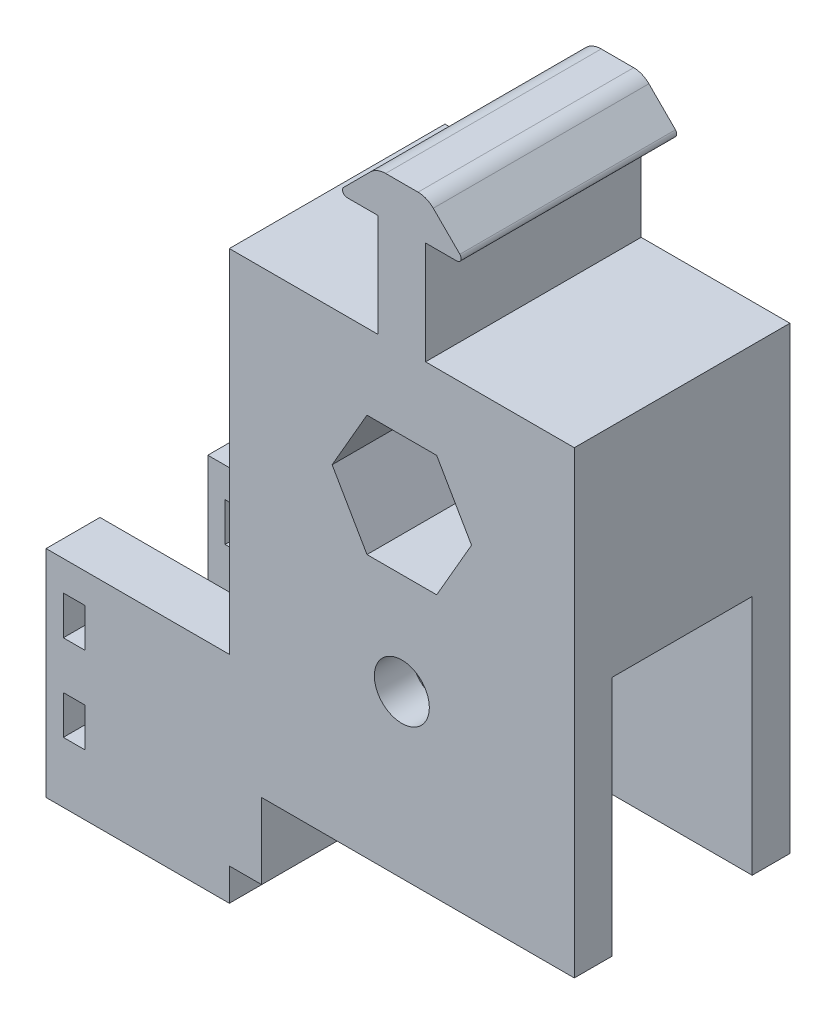
SolidWorks part; units mm, degrees
ref_plane "Front Plane" through (0, 0, 0) normal (0, 0, 1) x (1, 0, 0)
ref_plane "Top Plane" through (0, 0, 0) normal (0, 1, 0) x (1, 0, 0)
ref_plane "Right Plane" through (0, 0, 0) normal (1, 0, 0) x (0, 0, -1)
sketch "Sketch1" plane through (0, 0, 0) normal (0, 0, 1) x (1, 0, 0)
  line L0 (-20.32, 16.002) -> (-20.32, -38.1)
  line L1 (-4.1061, 7.112) -> (-8.2122, 0)
  line L2 (-8.2122, 0) -> (-4.1061, -7.112)
  line L3 (-4.1061, -7.112) -> (4.1061, -7.112)
  line L4 (4.1061, -7.112) -> (8.2122, 0)
  line L5 (8.2122, 0) -> (4.1061, 7.112)
  line L6 (4.1061, 7.112) -> (-4.1061, 7.112)
  line L7 (-20.32, -38.1) -> (20.32, -38.1)
  line L8 (20.32, -38.1) -> (20.32, 16.002)
  line L9 (-20.32, 16.002) -> (-2.794, 16.002)
  line L10 (-2.794, 16.002) -> (-2.794, 28.1305)
  line L11 (-2.794, 28.1305) -> (-6.477, 28.1305)
  line L12 (-6.8362, 28.9977) -> (-3.7065, 32.1275)
  line L13 (-1.9104, 32.8714) -> (1.9104, 32.8714)
  line L14 (0, 41.8096) -> (0, -25.778) construction
  line L15 (20.32, 16.002) -> (2.794, 16.002)
  line L16 (2.794, 16.002) -> (2.794, 28.1305)
  line L17 (6.8362, 28.9977) -> (3.7065, 32.1275)
  line L18 (2.794, 28.1305) -> (6.477, 28.1305)
  line L19 (-6.985, 28.6385) -> (6.985, 28.6385) construction
  circle A0 centre (0, 0) radius 7.112 construction
  arc A1 (-6.477, 28.1305) -> (-6.8362, 28.9977) centre (-6.477, 28.6385) cw
  arc A2 (-3.7065, 32.1275) -> (-1.9104, 32.8714) centre (-1.9104, 30.3314) cw
  arc A3 (3.7065, 32.1275) -> (1.9104, 32.8714) centre (1.9104, 30.3314) ccw
  arc A4 (6.477, 28.1305) -> (6.8362, 28.9977) centre (6.477, 28.6385) ccw
  point P18 (7.7034, 28.1305)
  point P21 (-4.6355, 28.1305)
  point P25 (-7.7034, 28.1305)
  point P29 (0, -38.1)
  point P35 (0, 32.8714)
  dimension "D7" = 0.508
  dimension "D8" = 2.54
  dimension "D1" = 14.224
  dimension "D2" = 21.0185
  dimension "D3" = 5.588
  dimension "D4" = 4.7409
  dimension "D5" = 135
  dimension "D6" = 13.97
  dimension "D9" = 38.1
  dimension "D10" = 8.89
  dimension "D11" = 20.32
extrude "Boss-Extrude1" add sketch "Sketch1" along normal mid plane 25.4
sketch "Sketch10" plane through (0, 0, 0) normal (0, 0, 1) x (1, 0, 0)
  line L0 (-20.32, -38.1) -> (-20.32, -46.99)
  line L1 (-20.32, -46.99) -> (-41.91, -46.99)
  line L2 (-41.91, -46.99) -> (-41.91, -50.8)
  line L3 (-41.91, -50.8) -> (-16.51, -50.8)
  line L4 (-16.51, -50.8) -> (-16.51, -38.1)
  line L5 (-20.32, -38.1) -> (20.32, -38.1) construction
  line L6 (-20.32, -38.1) -> (-16.51, -38.1)
  dimension "D2" = 8.89
  dimension "D3" = 3.81
  dimension "D4" = 21.59
extrude "Boss-Extrude4" add sketch "Sketch10" along normal up to surface and the other way up to surface up to face at (0, 18.0275, 12.7) other way up to face at (0, 18.0275, -12.7)
sketch "Sketch6" plane through (20.32, 0, 0) normal (1, 0, 0) x (0, 0, -1)
  line L0 (-12.7, -7.112) -> (12.7, -7.112) construction
  line L1 (-12.7, -7.112) -> (12.7, -7.112) construction
  line L2 (-8.255, -25.4) -> (-8.255, -9.652)
  line L3 (-8.255, -9.652) -> (8.255, -9.652)
  line L11 (-8.255, -25.4) -> (8.255, -25.4)
  line L12 (8.255, -9.652) -> (8.255, -25.4)
  point P10 (0, -9.652)
  dimension "D2" = 16.51
  dimension "D3" = 2.54
  dimension "D1" = 15.748
extrude "Cut-Extrude2" cut sketch "Sketch6" against normal through all
sketch "Sketch11" plane through (0, -46.99, 0) normal (0, 1, 0) x (1, 0, 0)
  line L0 (-41.91, -12.7) -> (-41.91, 12.7) construction
  line L1 (-20.32, -12.7) -> (-20.32, 12.7) construction
  line L2 (-41.91, -3.81) -> (-41.91, 3.81)
  line L3 (-20.32, -3.81) -> (-20.32, 3.81)
  line L4 (-41.91, 3.81) -> (-20.32, 3.81)
  line L5 (-41.91, -3.81) -> (-20.32, -3.81)
  point P8 (-20.32, 0)
  point P9 (-41.91, 0)
  dimension "D1" = 7.62
extrude "Cut-Extrude3" cut sketch "Sketch11" against normal up to surface (3.81 mm away) up to face at (-29.21, -50.8, 0)
sketch "Sketch15" plane through (0, 0, 12.7) normal (0, 0, 1) x (1, 0, 0)
  line L1 (-4.1061, -7.112) -> (4.1061, -7.112) construction
  circle A0 centre (0, -19.05) radius 3.2385
  point P7 (0, -7.112)
  dimension "D1" = 6.477
  dimension "D2" = 11.938
extrude "Cut-Extrude4" cut sketch "Sketch15" against normal up to surface (25.4 mm away) up to face at (-5.842, 4.643, -12.7)
sketch "Sketch16" plane through (20.32, 0, 0) normal (1, 0, 0) x (0, 0, -1)
  line L0 (-8.255, -25.4) -> (8.255, -25.4) construction
  line L1 (-8.255, -25.4) -> (8.255, -25.4)
  line L2 (-8.255, -25.4) -> (-8.255, -38.1)
  line L3 (-12.7, -38.1) -> (12.7, -38.1) construction
  line L4 (-8.255, -38.1) -> (8.255, -38.1)
  line L5 (8.255, -38.1) -> (8.255, -25.4)
extrude "Cut-Extrude5" cut sketch "Sketch16" against normal up to surface (36.83 mm away) up to face at (-16.51, -44.45, 0)
sketch "Sketch17" plane through (-20.32, 0, 0) normal (-1, 0, 0) x (0, 0, 1)
  line L0 (12.7, 16.002) -> (12.7, -46.99) construction
  line L1 (-3.81, -50.8) -> (-3.81, -46.99) construction
  line L2 (-3.81, -46.99) -> (-12.7, -46.99) construction
  line L3 (3.81, -50.8) -> (3.81, -46.99) construction
  line L4 (12.7, -46.99) -> (3.81, -46.99) construction
  line L5 (-3.81, -50.8) -> (3.81, -50.8) construction
  line L6 (-12.7, 16.002) -> (-12.7, -46.99) construction
  line L7 (12.7, -25.4) -> (12.7, -46.99)
  line L8 (-3.81, -50.8) -> (-3.81, -46.99)
  line L9 (-3.81, -46.99) -> (-12.7, -46.99)
  line L10 (3.81, -50.8) -> (3.81, -46.99)
  line L11 (12.7, -46.99) -> (3.81, -46.99)
  line L12 (-3.81, -50.8) -> (3.81, -50.8)
  line L13 (-12.7, -25.4) -> (-12.7, -46.99)
  line L14 (-12.7, -25.4) -> (12.7, -25.4)
  dimension "D1" = 21.59
extrude "Boss-Extrude5" add sketch "Sketch17" along normal blind 5.08
sketch "Sketch18" plane through (-25.4, 0, 0) normal (-1, 0, 0) x (0, 0, 1)
  line L0 (0, 0) -> (0, -56.8096) construction
  line L1 (-3.81, -46.99) -> (-12.7, -46.99) construction
  line L2 (-12.7, -25.4) -> (-12.7, -46.99) construction
  line L4 (-6.35, -46.99) -> (-12.7, -46.99)
  line L5 (-12.7, -25.4) -> (-12.7, -46.99)
  line L6 (12.7, -25.4) -> (-12.7, -25.4) construction
  line L7 (-6.35, -25.4) -> (-6.35, -46.99)
  line L8 (-6.35, -25.4) -> (-12.7, -25.4)
  line L9 (6.35, -25.4) -> (12.7, -25.4)
  line L10 (6.35, -25.4) -> (6.35, -46.99)
  line L11 (12.7, -25.4) -> (12.7, -46.99)
  line L12 (6.35, -46.99) -> (12.7, -46.99)
  dimension "D1" = 6.35
extrude "Boss-Extrude6" add sketch "Sketch18" along normal up to surface (16.51 mm away) up to face at (-41.91, -48.895, 8.255)
sketch "Sketch22" plane through (0, 0, 12.7) normal (0, 0, 1) x (1, 0, 0)
  line L0 (-20.32, -50.8) -> (-20.32, -46.99)
  line L1 (-16.51, -50.8) -> (-41.91, -50.8) construction
  line L2 (-20.32, -46.99) -> (-16.51, -46.99)
  line L4 (-16.51, -50.8) -> (-20.32, -50.8)
  line L5 (-16.51, -38.1) -> (-16.51, -50.8) construction
  line L6 (-16.51, -46.99) -> (-16.51, -50.8)
  dimension "D1" = 3.81
  dimension "D2" = 3.81
extrude "Cut-Extrude6" cut sketch "Sketch22" against normal up to surface (25.4 mm away) up to face at (-5.842, 6.802, -12.7)
sketch "Sketch23" plane through (0, 0, 12.7) normal (0, 0, 1) x (1, 0, 0)
  line L1 (-41.91, -25.4) -> (-20.32, -25.4) construction
  line L2 (-37.338, -25.4) -> (-37.338, -46.99) construction
  line L4 (-42.5372, -36.195) -> (-32.1388, -36.195) construction
  line L5 (-37.338, -28.9175) -> (-39.878, -28.9175)
  line L6 (-37.338, -28.9175) -> (-37.338, -33.4895)
  line L7 (-37.338, -33.4895) -> (-39.878, -33.4895)
  line L8 (-39.878, -28.9175) -> (-39.878, -33.4895)
  line L9 (-37.338, -39.0775) -> (-39.878, -39.0775)
  line L10 (-37.338, -39.0775) -> (-37.338, -43.6495)
  line L11 (-37.338, -43.6495) -> (-39.878, -43.6495)
  line L12 (-39.878, -39.0775) -> (-39.878, -43.6495)
  point P0 (-25.4, -25.4)
  point P20 (-37.338, -36.195)
  point P22 (-37.338, -36.195)
  point P23 (-39.878, -31.2035)
  point P24 (-39.878, -41.3635)
  dimension "D1" = 11.938
  dimension "D2" = 4.572
  dimension "D3" = 2.54
  dimension "D4" = 10.16
  dimension "D5" = 2.8825
extrude "Cut-Extrude7" cut sketch "Sketch23" against normal through all
